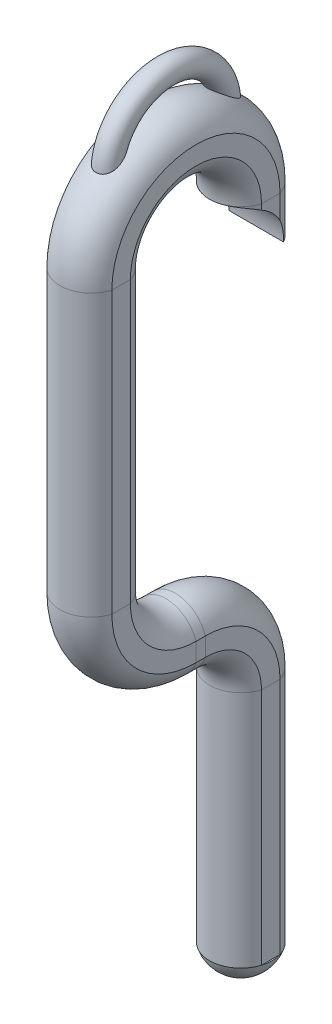
SolidWorks part; units mm, degrees
ref_plane "Front Plane" through (0, 0, 0) normal (1, 0, 0) x (0, 1, 0)
ref_plane "Top Plane" through (0, 0, 0) normal (0, 0, 1) x (0, 1, 0)
ref_plane "Right Plane" through (0, 0, 0) normal (0, 1, 0) x (-1, 0, 0)
sketch "Sketch1" plane through (0, 0, 0) normal (1, 0, 0) x (0, 1, 0)
  line L0 (0, 0) -> (64.77, 0)
  line L1 (82.55, 17.78) -> (82.55, 20.32)
  line L2 (102.87, 40.64) -> (179.07, 40.64)
  line L3 (179.07, 0) -> (166.37, 0)
  arc A0 (64.77, 0) -> (82.55, 17.78) centre (64.77, 17.78) ccw
  arc A1 (82.55, 20.32) -> (102.87, 40.64) centre (102.87, 20.32) cw
  arc A2 (179.07, 40.64) -> (179.07, 0) centre (179.07, 20.32) cw
  dimension "D1" = 20.32
  dimension "D3" = 17.78
  dimension "D4" = 20.32
  dimension "D2" = 82.55
  dimension "D5" = 40.64
  dimension "D6" = 76.2
  dimension "D7" = 12.7
sketch "Sketch2" plane through (0, 0, 0) normal (0, 1, 0) x (-1, 0, 0)
  line L0 (-8.128, 2.5146) -> (-8.128, -2.5146)
  line L1 (0, 17.78) -> (0, 0) construction
  line L2 (0, 17.78) -> (0, 0) construction
  line L3 (8.128, 2.5146) -> (8.128, -2.5146)
  line L4 (-8.128, 0) -> (0, 0) construction
  arc A1 (8.128, 2.5146) -> (-8.128, 2.5146) centre (0, -0.0031) ccw
  arc A2 (8.128, -2.5146) -> (-8.128, -2.5146) centre (0, 0.0031) cw
  dimension "D2" = 16.256
  dimension "D3" = 8.509
  dimension "D1" = 5.0292
sweep "Sweep1" add profiles "Sketch2" path "Sketch1"
sketch "Sketch3" plane through (0, 0, 0) normal (1, 0, 0) x (0, 1, 0)
  line L0 (0, 8.5059) -> (0, 0)
  line L1 (0, 0) -> (-6.35, 0)
  line L2 (-6.35, 0) -> (-6.35, -5.3286) construction
  line L3 (166.37, -2.5146) -> (166.37, 2.5146) construction
  line L4 (179.07, 8.5059) -> (166.37, 8.5059) construction
  line L5 (166.37, -4.1941) -> (166.37, 8.5059)
  line L6 (166.37, 8.5059) -> (179.07, 8.5059)
  line L7 (179.07, 32.1341) -> (179.07, 8.5059) construction
  line L8 (179.07, 20.32) -> (199.39, 20.32) construction
  arc A0 (0, 8.5059) -> (-6.35, 0) centre (2.5219, 0) ccw
  arc A1 (179.07, 8.5059) -> (166.37, -4.1941) centre (166.37, 8.5059) cw
  arc A2 (199.39, 36.195) -> (199.39, 4.445) centre (199.39, 20.32) cw
  dimension "D4" = 15.875
  dimension "D1" = 6.35
  dimension "D2" = 12.7
  dimension "D3" = 20.32
sweep "Sweep2" add path "Sketch3" circular profile diameter 6.35 parameters "D3"=6.35
revolve "Revolve1" add sketch "Sketch3<3>" angle 360 about L1 region at (0, -2.6387, 3.4262)
sketch "Sketch3<3>" plane through (0, 0, 0) normal (1, 0, 0) x (0, 1, 0) same geometry as "Sketch3"
extrude "Cut-Extrude1" cut sketch "Sketch3<4>" against normal through all both and the other way through all contours L6 A1 L5
sketch "Sketch3<4>" plane through (0, 0, 0) normal (1, 0, 0) x (0, 1, 0) same geometry as "Sketch3"
